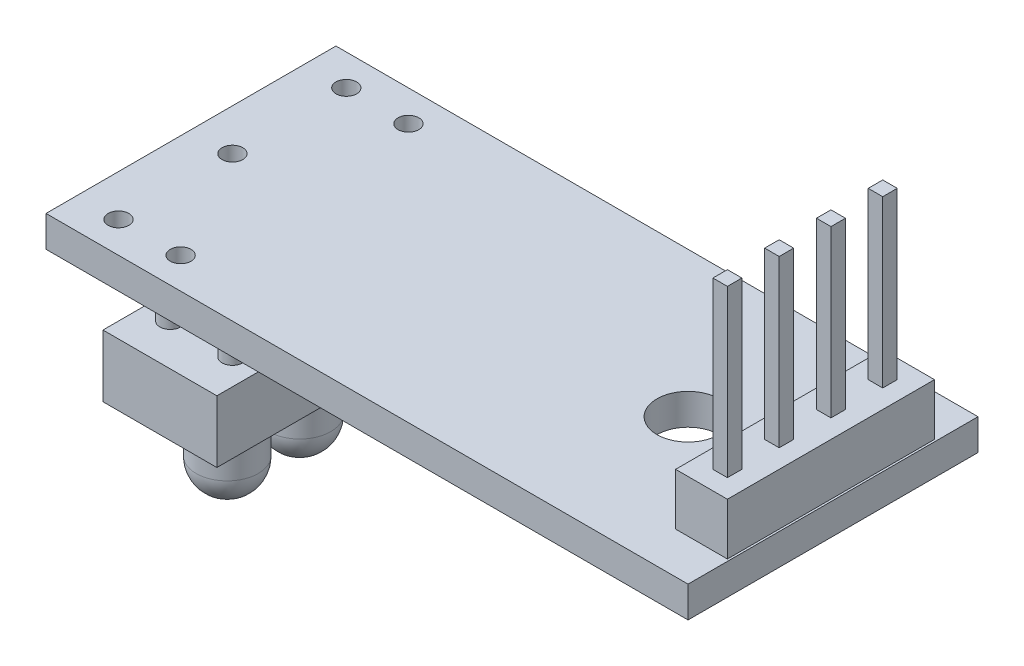
SolidWorks part; units mm, degrees
ref_plane "Front Plane" through (0, 0, 0) normal (0, 0, 1) x (1, 0, 0)
ref_plane "Top Plane" through (0, 0, 0) normal (0, 1, 0) x (1, 0, 0)
ref_plane "Right Plane" through (0, 0, 0) normal (1, 0, 0) x (0, 0, -1)
sketch "Sketch1" plane through (0, 0, 0) normal (0, 1, 0) x (1, 0, 0)
  line L1 (0, 0) -> (-31, 0)
  line L2 (0, 0) -> (0, -14)
  line L3 (0, -14) -> (-31, -14)
  line L4 (-31, 0) -> (-31, -14)
  circle A0 centre (-7, -7) radius 1.5
  dimension "D3" = 3
  dimension "D1" = 31
  dimension "D2" = 14
  dimension "D4" = 7
  dimension "D5" = 7
extrude "Boss-Extrude1" add sketch "Sketch1" along normal blind 1.5
sketch "Sketch2" plane through (0, 1.5, 0) normal (0, 1, 0) x (1, 0, 0)
  line L0 (0, -14) -> (0, 0) construction
  line L1 (-2.6, -2) -> (-0.1, -2)
  line L2 (-2.6, -2) -> (-2.6, -12)
  line L3 (-2.6, -12) -> (-0.1, -12)
  line L4 (-0.1, -2) -> (-0.1, -12)
  line L5 (-31, -14) -> (0, -14) construction
  dimension "D1" = 10
  dimension "D2" = 2.5
  dimension "D3" = 0.1
  dimension "D4" = 2
extrude "Boss-Extrude2" add sketch "Sketch2" along normal blind 2.5
sketch "Sketch3" plane through (0, 4, 0) normal (0, 1, 0) x (1, 0, 0)
  line L0 (-0.1, -2) -> (-2.6, -2) construction
  line L1 (-1.7, -2.9) -> (-1, -2.9)
  line L2 (-1.7, -2.9) -> (-1.7, -3.6)
  line L3 (-1.7, -3.6) -> (-1, -3.6)
  line L4 (-1, -2.9) -> (-1, -3.6)
  line L5 (-1.7, -5.4) -> (-1, -5.4)
  line L6 (-1.7, -5.4) -> (-1.7, -6.1)
  line L7 (-1.7, -6.1) -> (-1, -6.1)
  line L8 (-1, -5.4) -> (-1, -6.1)
  line L9 (-1.7, -7.9) -> (-1, -7.9)
  line L10 (-1.7, -7.9) -> (-1.7, -8.6)
  line L11 (-1.7, -8.6) -> (-1, -8.6)
  line L12 (-1, -7.9) -> (-1, -8.6)
  line L13 (-1.7, -10.4) -> (-1, -10.4)
  line L14 (-1.7, -10.4) -> (-1.7, -11.1)
  line L15 (-1.7, -11.1) -> (-1, -11.1)
  line L16 (-1, -10.4) -> (-1, -11.1)
  line L18 (-2.6, -2) -> (-2.6, -12) construction
  dimension "D1" = 0.7
  dimension "D2" = 0.7
  dimension "D3" = 0.7
  dimension "D4" = 0.7
  dimension "D5" = 0.7
  dimension "D6" = 0.7
  dimension "D7" = 0.7
  dimension "D8" = 0.7
  dimension "D9" = 0.9
  dimension "D10" = 1.8
  dimension "D11" = 1.8
  dimension "D12" = 1.8
  dimension "D13" = 0.9
  dimension "D14" = 0.9
  dimension "D15" = 0.9
  dimension "D16" = 0.9
extrude "Boss-Extrude3" add sketch "Sketch3" along normal blind 8
sketch "Sketch13" plane through (0, 1.5, 0) normal (0, 1, 0) x (0, 0, 1)
  line L0 (14, -31) -> (14, 0) construction
  line L1 (0, 0) -> (0, -31) construction
  line L2 (0, 0) -> (0, -31) construction
  line L3 (0, -31) -> (14, -31) construction
  circle A0 centre (12.5, -29) radius 0.5
  circle A1 centre (12.5, -26) radius 0.5
  circle A2 centre (10, -26) radius 0.5
  circle A3 centre (10, -29) radius 0.5
  circle A4 centre (7, -29) radius 0.5
  circle A5 centre (4, -29) radius 0.5
  circle A6 centre (1.5, -29) radius 0.5
  circle A7 centre (4, -26) radius 0.5
  circle A8 centre (1.5, -26) radius 0.5
  dimension "D1" = 1
  dimension "D2" = 1
  dimension "D3" = 1
  dimension "D4" = 1
  dimension "D5" = 1
  dimension "D6" = 1
  dimension "D7" = 1
  dimension "D8" = 1
  dimension "D9" = 1
  dimension "D10" = 7
  dimension "D11" = 1.5
  dimension "D12" = 1.5
  dimension "D13" = 1.5
  dimension "D14" = 1.5
  dimension "D15" = 4
  dimension "D16" = 4
  dimension "D17" = 4
  dimension "D18" = 4
  dimension "D19" = 2
  dimension "D20" = 2
  dimension "D21" = 2
  dimension "D22" = 2
  dimension "D23" = 5
  dimension "D24" = 5
  dimension "D25" = 5
  dimension "D26" = 5
  dimension "D27" = 2
extrude "Cut-Extrude3" cut sketch "Sketch13" against normal up to next
ref_plane "Plane1" through (0, -4, 0) normal (0, -1, 0) x (0, 0, -1)
sketch "Sketch14" plane through (0, -4, 0) normal (0, -1, 0) x (0, 0, -1)
  line L0 (-14, -31) -> (-14, 0) construction
  line L1 (-12, -24.75) -> (-2, -24.75)
  line L2 (-12, -24.75) -> (-12, -30.25)
  line L3 (-12, -30.25) -> (-2, -30.25)
  line L4 (-2, -24.75) -> (-2, -30.25)
  line L5 (0, -31) -> (-14, -31) construction
  dimension "D1" = 10
  dimension "D2" = 5.5
  dimension "D3" = 2
  dimension "D4" = 0.75
extrude "Boss-Extrude10" add sketch "Sketch14" along normal blind 4 separate body
chamfer "Chamfer1" distance 1 4 edges at (-27.5, -8, 2) (-30.25, -8, 7) (-27.5, -8, 12) (-24.75, -8, 7)
sketch "Sketch15" plane through (0, -8, 0) normal (0, -1, 0) x (0, 0, -1)
  line L1 (-11, -29.25) -> (-3, -29.25) construction
  line L2 (-11, -25.75) -> (-11, -29.25) construction
  line L3 (-3, -29.25) -> (-3, -25.75) construction
  circle A0 centre (-8.75, -27.5) radius 1.5
  circle A1 centre (-5.25, -27.5) radius 1.5
  dimension "D1" = 3
  dimension "D4" = 3
  dimension "D2" = 1.75
  dimension "D3" = 2.25
  dimension "D5" = 1.75
  dimension "D6" = 2.25
extrude "Boss-Extrude11" add sketch "Sketch15" along normal blind 3
extrude "Boss-Extrude12" add sketch "Sketch15<2>" against normal blind 2
sketch "Sketch15<2>" plane through (0, -8, 0) normal (0, -1, 0) x (0, 0, -1) same geometry as "Sketch15"
fillet "Fillet3" radius 1.5 1 edges at (-27.5, -11, 7.25)
fillet "Fillet4" radius 1.5 1 edges at (-27.5, -11, 3.75)
sketch "Sketch16" plane through (0, -4, 0) normal (0, -1, 0) x (0, 0, -1)
  circle A0 centre (-10, -26) radius 0.5
  circle A2 centre (-4, -29) radius 0.5
  circle A3 centre (-4, -26) radius 0.5
  circle A4 centre (-10, -29) radius 0.5
  dimension "D1" = 1
  dimension "D2" = 1
  dimension "D3" = 1
  dimension "D4" = 1
extrude "Boss-Extrude13" add sketch "Sketch16" against normal blind 5.5
